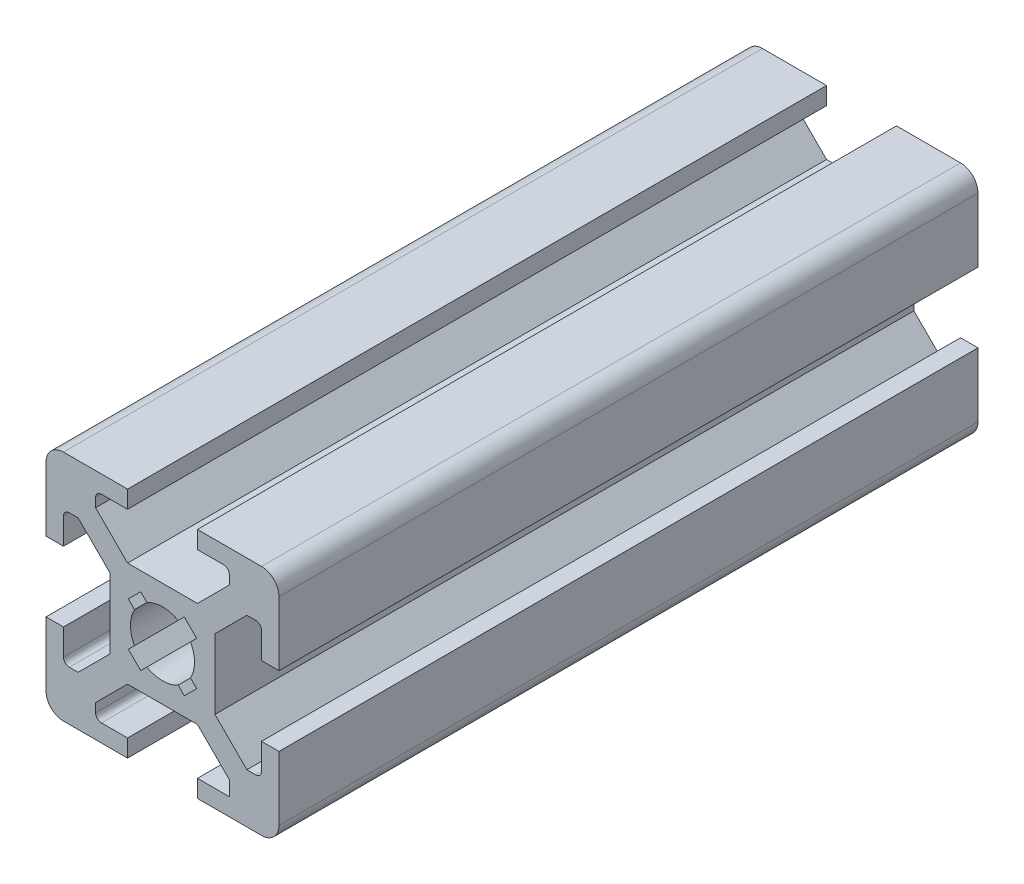
SolidWorks part; units mm, degrees
ref_plane "Alzado" through (0, 0, 0) normal (0, 0, 1) x (1, 0, 0)
ref_plane "Planta" through (0, 0, 0) normal (0, 1, 0) x (1, 0, 0)
ref_plane "Vista lateral" through (0, 0, 0) normal (1, 0, 0) x (0, 0, -1)
sketch "Croquis1" plane through (0, 0, 0) normal (0, 0, 1) x (1, 0, 0)
  line L0 (3, -4.5) -> (5.7414, -7.2414)
  line L1 (-10, 10) -> (-3, 10)
  line L2 (-10, 10) -> (-10, 3)
  line L3 (-10, -10) -> (-3, -10)
  line L4 (10, 10) -> (10, 3)
  line L5 (-10, 10) -> (10, -10) construction
  line L6 (-10, -10) -> (10, 10) construction
  line L7 (-3, 4.5) -> (3, 4.5)
  line L8 (-4.5, 3) -> (-4.5, -3)
  line L9 (-3, -4.5) -> (3, -4.5)
  line L10 (4.5, 3) -> (4.5, -3)
  line L11 (-4.5, 4.5) -> (4.5, -4.5) construction
  line L12 (-4.5, -4.5) -> (4.5, 4.5) construction
  line L13 (5.7414, -7.2414) -> (5.7414, -8.5)
  line L14 (5.7414, -8.5) -> (3, -8.5)
  line L15 (3, -8.5) -> (3, -10)
  line L16 (-7.2414, 5.7414) -> (-4.5, 3)
  line L17 (-3, -10) -> (-3, -8.5)
  line L18 (-3, -8.5) -> (-5.7414, -8.5)
  line L19 (-5.7414, -8.5) -> (-5.7414, -7.2414)
  line L20 (-5.7414, -7.2414) -> (-3, -4.5)
  line L21 (0, -4.5) -> (0, -10) construction
  line L22 (3, -10) -> (10, -10)
  line L24 (-4.5, -3) -> (-7.2414, -5.7414)
  line L25 (-7.2414, -5.7414) -> (-8.5, -5.7414)
  line L26 (-8.5, -5.7414) -> (-8.5, -3)
  line L27 (-8.5, -3) -> (-10, -3)
  line L28 (-10, 3) -> (-8.5, 3)
  line L29 (-8.5, 3) -> (-8.5, 5.7414)
  line L30 (-8.5, 5.7414) -> (-7.2414, 5.7414)
  line L31 (5.7414, 7.2414) -> (3, 4.5)
  line L33 (-3, 4.5) -> (-5.7414, 7.2414)
  line L34 (-5.7414, 7.2414) -> (-5.7414, 8.5)
  line L35 (-5.7414, 8.5) -> (-3, 8.5)
  line L36 (-3, 8.5) -> (-3, 10)
  line L37 (3, 10) -> (3, 8.5)
  line L38 (3, 8.5) -> (5.7414, 8.5)
  line L39 (5.7414, 8.5) -> (5.7414, 7.2414)
  line L40 (7.2414, -5.7414) -> (4.5, -3)
  line L42 (4.5, 3) -> (7.2414, 5.7414)
  line L43 (7.2414, 5.7414) -> (8.5, 5.7414)
  line L44 (8.5, 5.7414) -> (8.5, 3)
  line L45 (8.5, 3) -> (10, 3)
  line L46 (10, -3) -> (8.5, -3)
  line L47 (8.5, -3) -> (8.5, -5.7414)
  line L48 (8.5, -5.7414) -> (7.2414, -5.7414)
  line L49 (3, 10) -> (10, 10)
  line L50 (-10, -3) -> (-10, -10)
  line L51 (10, -3) -> (10, -10)
  line L52 (3, 4.5) -> (-3, 4.5) [skipped]
  line L53 (-4.5, 3) -> (-4.5, -3) [skipped]
  line L54 (4.5, -3) -> (4.5, 3) [skipped]
  point P0 (0, 0)
  point P6 (0, 0)
  point P26 (0, 0)
  point P37 (0, 0)
  point P48 (0, 0)
  point P59 (0, 0)
  dimension "D1" = 20
  dimension "D2" = 1.5
  dimension "D3" = 9
  dimension "D4" = 7
  dimension "D5" = 6
  dimension "D6" = 4
  dimension "D7" = 5.5
extrude "Saliente-Extruir1" add sketch "Croquis1" along normal blind 60
fillet "Redondeo1" radius 1.5 4 edges at (10, -10, 30) (-10, -10, 30) (10, 10, 30) (-10, 10, 30)
fillet "Redondeo2" radius 0.5 7 edges at (-5.7414, -8.5, 30) (5.7414, 8.5, 30) (-5.7414, 8.5, 30) (8.5, -5.7414, 30) (-8.5, -5.7414, 30) (8.5, 5.7414, 30) (-8.5, 5.7414, 30)
sketch "Croquis2" plane through (0, 0, 0) normal (0, 0, -1) x (-1, 0, 0)
  line L0 (-1.3405, 2.4012) -> (-1.8708, 2.9315)
  line L1 (-1.8708, 2.9315) -> (-2.9315, 1.8708)
  line L2 (-2.9315, 1.8708) -> (-2.4012, 1.3405)
  line L3 (-4.5, 3) -> (-7.2414, 5.7414) construction
  line L5 (1.8708, 2.9315) -> (1.3405, 2.4012)
  line L6 (2.9315, 1.8708) -> (1.8708, 2.9315)
  line L7 (2.4012, 1.3405) -> (2.9315, 1.8708)
  line L8 (2.9315, -1.8708) -> (2.4012, -1.3405)
  line L9 (1.8708, -2.9315) -> (2.9315, -1.8708)
  line L10 (1.3405, -2.4012) -> (1.8708, -2.9315)
  line L11 (-1.8708, -2.9315) -> (-1.3405, -2.4012)
  line L12 (-2.9315, -1.8708) -> (-1.8708, -2.9315)
  line L13 (-2.4012, -1.3405) -> (-2.9315, -1.8708)
  arc A0 (-2.4012, 1.3405) -> (-2.4012, -1.3405) centre (0, 0) ccw
  arc A1 (-1.3405, -2.4012) -> (1.3405, -2.4012) centre (0, 0) ccw
  arc A2 (2.4012, -1.3405) -> (2.4012, 1.3405) centre (0, 0) ccw
  arc A3 (1.3405, 2.4012) -> (-1.3405, 2.4012) centre (0, 0) ccw
  point P25 (0, 0)
  dimension "D1" = 5.5
  dimension "D2" = 0.75
  dimension "D3" = 1.5
  dimension "D4" = 4
extrude "Cortar-Extruir1" cut sketch "Croquis2" against normal through all
